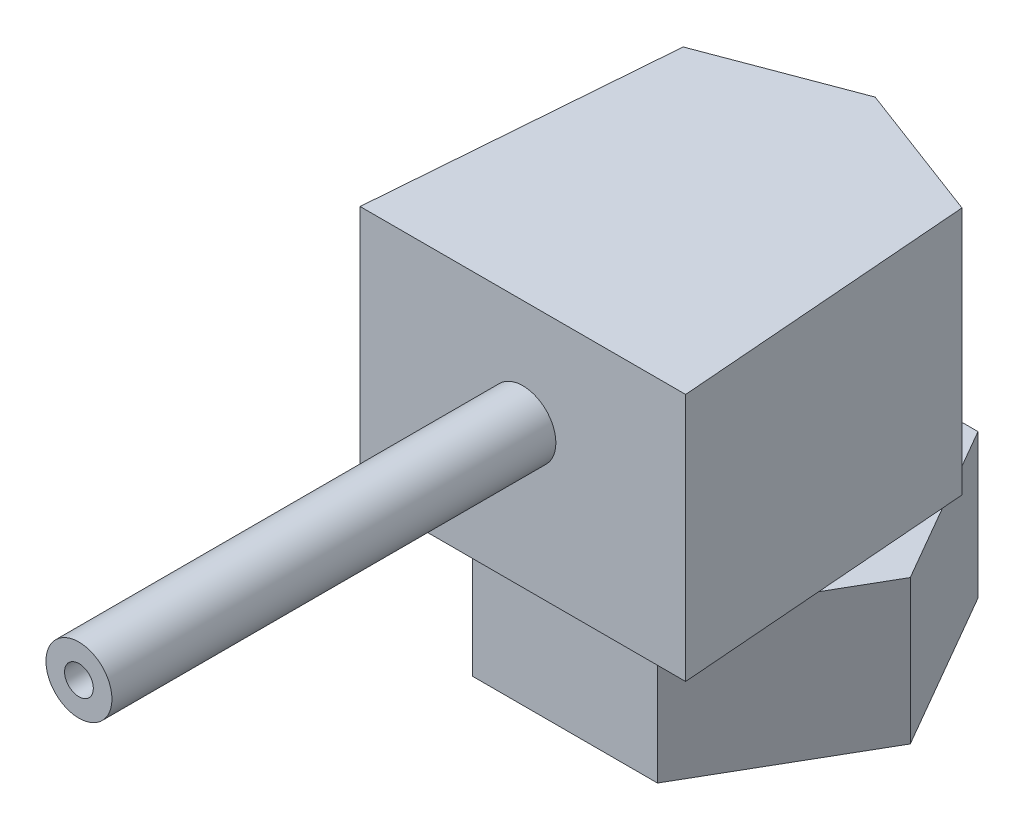
SolidWorks part; units mm, degrees
ref_plane "Front Plane" through (0, 0, 0) normal (0, 0, 1) x (1, 0, 0)
ref_plane "Top Plane" through (0, 0, 0) normal (0, 1, 0) x (1, 0, 0)
ref_plane "Right Plane" through (0, 0, 0) normal (1, 0, 0) x (0, 0, -1)
sketch "Sketch1" plane through (0, 0, 0) normal (0, 1, 0) x (1, 0, 0)
  line L1 (6.2527, 0) -> (3.1264, 5.415)
  line L2 (3.1264, 5.415) -> (-3.1264, 5.415)
  line L3 (-3.1264, 5.415) -> (-6.2527, 0)
  line L4 (-6.2527, 0) -> (-3.1264, -5.415)
  line L5 (-3.1264, -5.415) -> (3.1264, -5.415)
  line L6 (3.1264, -5.415) -> (6.2527, 0)
  circle A0 centre (0, 0) radius 5.415 construction
  dimension "D1" = 10.83
extrude "Boss-Extrude1" add sketch "Sketch1" along normal blind 4.87
sketch "Sketch2" plane through (0, 4.87, 0) normal (0, 1, 0) x (1, 0, 0)
  line L0 (0, 5.0658) -> (-4.7103, 3.2896)
  line L1 (-4.7103, 3.2896) -> (-5.5, -6.8373)
  line L2 (-5.5, -6.8373) -> (-1.5285, -6.8373)
  line L3 (0, 0) -> (0, 7.4509) construction
  line L4 (5.5, -6.8373) -> (-1.5285, -6.8373)
  line L5 (4.7103, 3.2896) -> (5.5, -6.8373)
  line L6 (0, 5.0658) -> (4.7103, 3.2896)
  point P10 (-3.1818, 3.2896)
  point P11 (0, -6.8373)
  dimension "D1" = 11
extrude "Boss-Extrude2" add sketch "Sketch2" along normal blind 8.4
sketch "Sketch3" plane through (0, 0, 6.8373) normal (0, 0, 1) x (1, 0, 0)
  line L1 (-3.1264, 0) -> (3.1264, 0) construction
  circle A0 centre (0, 9.66) radius 0.4858
  circle A1 centre (0, 9.66) radius 1.115
  point P3 (0, 0)
  dimension "D1" = 2.23
  dimension "D2" = 9.66
extrude "Boss-Extrude3" add sketch "Sketch3" along normal blind 15
sketch "Sketch4" plane through (0, 0, 0) normal (0, -1, 0) x (1, 0, 0)
  circle A0 centre (0, 0) radius 2.8864
extrude "Boss-Extrude4" add sketch "Sketch4" along normal blind 0.5
